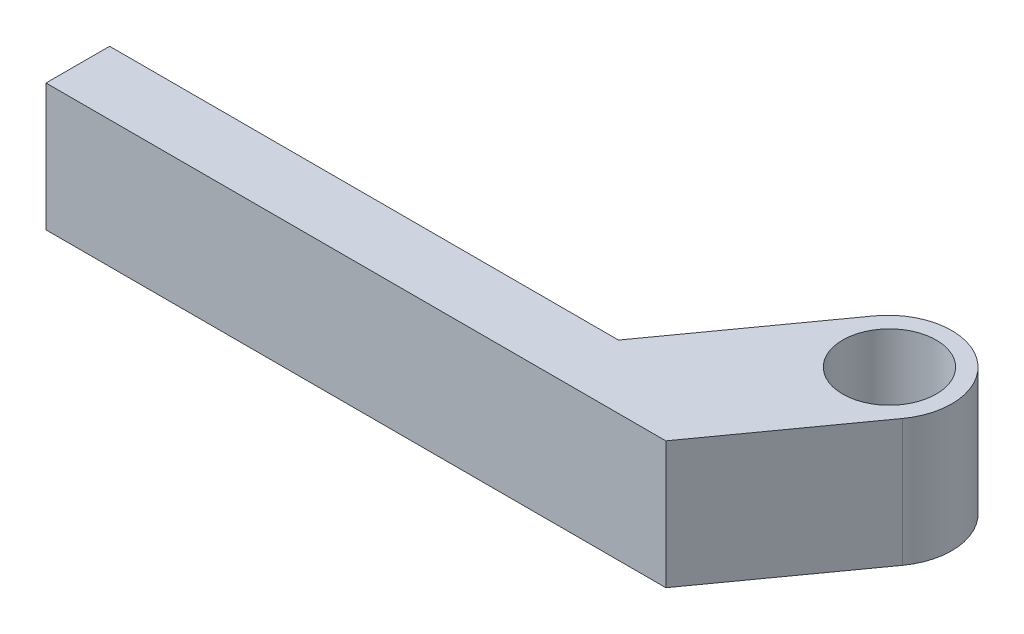
SolidWorks part; units mm, degrees
ref_plane "Front Plane" through (0, 0, 0) normal (0, 0, 1) x (1, 0, 0)
ref_plane "Top Plane" through (0, 0, 0) normal (0, 1, 0) x (1, 0, 0)
ref_plane "Right Plane" through (0, 0, 0) normal (1, 0, 0) x (0, 0, -1)
sketch "Sketch2" plane through (0, 0, 0) normal (0, 1, 0) x (1, 0, 0)
  line L5 (-10.6389, -35.243) -> (0.0062, -20.4255)
  line L7 (-61.4389, -41.593) -> (-10.6389, -41.593)
  line L8 (-61.4389, -41.593) -> (-61.4389, -35.243)
  line L9 (-61.4389, -35.243) -> (-10.6389, -35.243)
  line L10 (-10.6389, -41.593) -> (-10.6389, -35.243) construction
  line L11 (-61.4389, -41.593) -> (-10.6389, -35.243) construction
  line L12 (-61.4389, -35.243) -> (-10.6389, -41.593) construction
  line L14 (-10.6389, -41.593) -> (0.4368, -41.593)
  line L18 (10.3205, -27.8354) -> (0.4368, -41.593)
  line L19 (0.0062, -20.4255) -> (10.3205, -27.8354) construction
  line L20 (5.1633, -17.7805) -> (-45.4817, -17.7805) construction
  arc A2 (0.0062, -20.4255) -> (10.3205, -27.8354) centre (5.1633, -24.1305) cw
  point P5 (-36.0389, -38.418)
  dimension "D2" = 12.7
  dimension "D3" = 17.4625
  dimension "D4" = 6.35
  dimension "D10" = 50.8
extrude "Boss-Extrude1" add sketch "Sketch2" along normal blind 12.7
hole_wizard "U (0.368) Diameter Hole1" positions "Sketch3" profile "Sketch4" hole size "U" standard "ANSI Inch" end condition through all
sketch "Sketch3" plane through (0, 12.7, 0) normal (0, 1, 0) x (1, 0, 0)
  line L0 (0.4368, -41.593) -> (10.3205, -27.8354) construction
  arc A0 (10.3205, -27.8354) -> (0.0062, -20.4255) centre (5.1633, -24.1305) ccw construction
  point P0 (5.2187, -24.0534)
  point P6 (8.8683, -18.9734)
  dimension "D1" = 5.08
  dimension "D2" = 6.35
sketch "Sketch4" plane through (5.2187, 12.7, 24.0534) normal (1, 0, 0) x (0, 0, 1)
  line L0 (0, 0) -> (0, 12.7)
  line L1 (0, 12.7) -> (4.6736, 12.7)
  line L2 (4.6736, 12.7) -> (4.6736, 0)
  line L5 (4.6736, 0) -> (0, 0)
  line L11 (0, -6.35) -> (0, 107.95) construction
  dimension "Thru Hole Dia." = 9.3472
  dimension "Thru Hole Depth" = 12.7
sketch "Sketch5" plane through (0, 12.7, 0) normal (0, 1, 0) x (1, 0, 0)
  line L0 (5.1633, -17.7805) -> (-38.0048, -17.7805) construction
  arc A0 (10.3205, -27.8354) -> (0.0062, -20.4255) centre (5.1633, -24.1305) ccw construction
